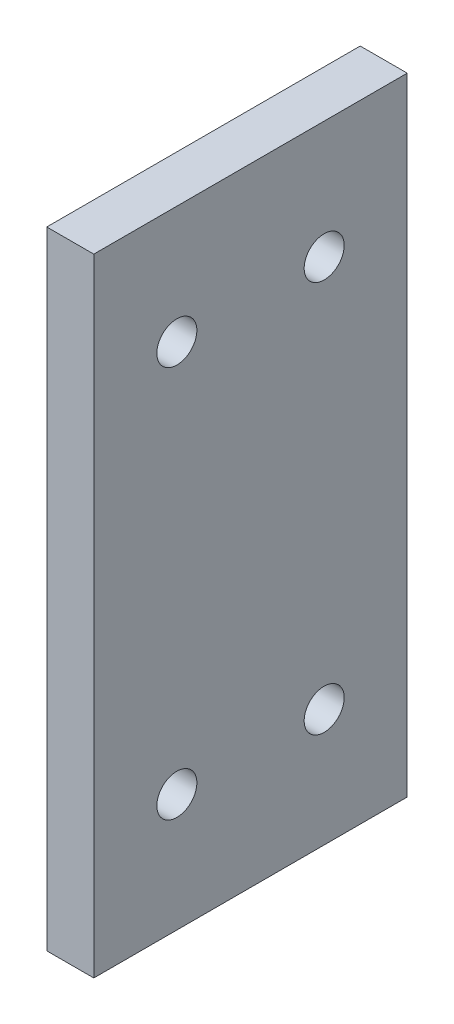
SolidWorks part; units mm, degrees
ref_plane "Front Plane" through (0, 0, 0) normal (1, 0, 0) x (0, 1, 0)
ref_plane "Top Plane" through (0, 0, 0) normal (0, 0, 1) x (0, 1, 0)
ref_plane "Right Plane" through (0, 0, 0) normal (0, 1, 0) x (-1, 0, 0)
sketch "Sketch1" plane through (0, 0, 0) normal (1, 0, 0) x (0, 1, 0)
  line L7 (-40, -20) -> (40, -20)
  line L8 (-40, -20) -> (-40, 20)
  line L9 (-40, 20) -> (40, 20)
  line L10 (40, -20) -> (40, 20)
  line L11 (-40, -20) -> (40, 20) construction
  line L12 (-40, 20) -> (40, -20) construction
  line L13 (-25, -9.4) -> (25, -9.4) construction
  line L14 (-25, -9.4) -> (-25, 9.4) construction
  line L15 (-25, 9.4) -> (25, 9.4) construction
  line L16 (25, -9.4) -> (25, 9.4) construction
  line L17 (-25, -9.4) -> (25, 9.4) construction
  line L18 (-25, 9.4) -> (25, -9.4) construction
  circle A0 centre (-25, 9.4) radius 2.555
  circle A1 centre (-25, -9.4) radius 2.555
  circle A2 centre (25, -9.4) radius 2.555
  circle A3 centre (25, 9.4) radius 2.555
  point P0 (0, 0)
  point P2 (0, 0)
  dimension "D5" = 5.11
  dimension "D6" = 5.11
  dimension "D7" = 5.11
  dimension "D8" = 5.11
  dimension "D1" = 80
  dimension "D2" = 40
  dimension "D3" = 10.6
  dimension "D4" = 50
extrude "Boss-Extrude2" add sketch "Sketch1" along normal blind 6 contours L7 L10 L9 L8
extrude "Cut-Extrude3" cut sketch "Sketch1<3>" along normal up to next contours A0 | A3 | A2 | A1
sketch "Sketch1<3>" plane through (0, 0, 0) normal (1, 0, 0) x (0, 1, 0) same geometry as "Sketch1"
